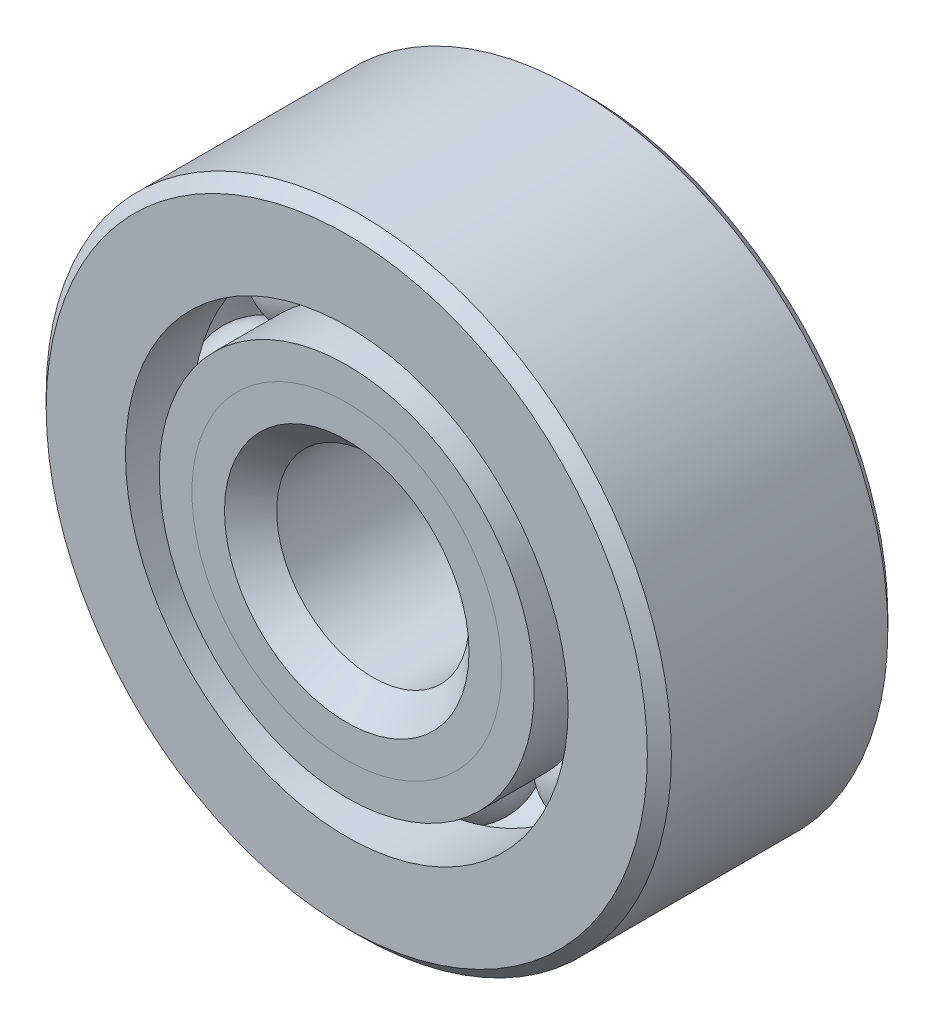
SolidWorks part; units mm, degrees
ref_plane "Front Plane" through (0, 0, 0) normal (0, 0, 1) x (1, 0, 0)
ref_plane "Top Plane" through (0, 0, 0) normal (0, 1, 0) x (1, 0, 0)
ref_plane "Right Plane" through (0, 0, 0) normal (1, 0, 0) x (0, 0, -1)
sketch "Sketch1" plane through (0, 0, 0) normal (1, 0, 0) x (0, 0, -1)
  line L0 (-2.5, 0) -> (2.5, 0) construction
  line L1 (0, 6.5) -> (0, -6.5) construction
  line L2 (2.25, 6.5) -> (-2.25, 6.5)
  line L3 (-2.25, 6.5) -> (-2.5, 6.25)
  line L4 (-2.5, 6.25) -> (-2.5, 4.6016)
  line L5 (-2.5, 4.6016) -> (-1.1111, 4.6016)
  line L6 (2.5, 4.6016) -> (1.1111, 4.6016)
  line L7 (2.5, 6.25) -> (2.5, 4.6016)
  line L8 (2.25, 6.5) -> (2.5, 6.25)
  line L9 (0, 6.5) -> (0, 4.25) construction
  line L10 (0, 4.25) -> (0, 2) construction
  line L11 (-2.5, -6.5) -> (2.5, -6.5) construction
  line L12 (0, -2) -> (0, 2) construction
  line L13 (2.5, -2) -> (2.5, 2) construction
  arc A0 (-1.1111, 4.6016) -> (1.1111, 4.6016) centre (0, 4.25) cw
  point P14 (0, 2)
  point P15 (0, -2)
  point P19 (0, -6.5)
  point P23 (0, 0)
  point P25 (2.5, 0)
  dimension "OD" = 13
  dimension "D1" = 45
  dimension "D2" = 0.25
  dimension "D3" = 2.2222
  dimension "D4" = 0.3516
  dimension "Width" = 5
  dimension "Shaft Dia" = 4
revolve "Revolve1" add sketch "Sketch1" angle 360 about L0
sketch "Sketch2" plane through (0, 0, 0) normal (1, 0, 0) x (0, 0, -1)
  line L0 (-2.5, 3.8984) -> (-1.1111, 3.8984)
  line L1 (-2.5, 6.25) -> (-2.5, -6.25) construction
  line L2 (-2.5, 3.8984) -> (-2.5, 3.2203)
  line L3 (-2.5, 3.2203) -> (-1.822, 2.5423)
  line L4 (-1.822, 2.5423) -> (0, 2.5423)
  line L5 (0, 6.5) -> (0, -6.5) construction
  line L6 (0, 2.5423) -> (0, 3.0846)
  line L7 (0, 3.0846) -> (0, 2) construction
  line L8 (-2.5, 3.8984) -> (-2.5, 2.5423) construction
  line L9 (-2.5, 2.5423) -> (-1.822, 2.5423) construction
  arc A0 (-1.1111, 3.8984) -> (0, 3.0846) centre (0, 4.25) ccw
  arc A1 (1.1111, 4.6016) -> (-1.1111, 4.6016) centre (0, 4.25) ccw construction
  circle A2 centre (0, 4.25) radius 1.1654 construction
  dimension "D1" = 45
revolve "Revolve2" add sketch "Sketch2" angle 360 about L0
sketch "Sketch3" plane through (0, 0, 0) normal (1, 0, 0) x (0, 0, -1)
  line L0 (-2.5, 3.2203) -> (-1.822, 2.5423)
  line L1 (-1.822, 2.5423) -> (0, 2.5423)
  line L2 (0, 2.5423) -> (0, 3.0846)
  line L3 (-2.5, 3.2203) -> (-2.5, 2.5423)
  line L4 (-2.5, 3.8984) -> (-2.5, 2.5423) construction
  line L5 (-2.5, 2.5423) -> (-1.9577, 2)
  line L6 (-1.9577, 2) -> (2.25, 2)
  line L7 (2.25, 6.5) -> (2.25, -6.5) construction
  line L8 (2.25, 2) -> (2.5, 2.25)
  line L9 (2.5, -6.25) -> (2.5, 6.25) construction
  line L10 (2.5, 2.25) -> (2.5, 3.8984)
  line L11 (2.5, 3.8984) -> (1.1111, 3.8984)
  line L13 (2.25, 6.5) -> (2.5, 6.25) construction
  circle A0 centre (0, 4.25) radius 1.1654 construction
  arc A1 (1.1111, 3.8984) -> (0, 3.0846) centre (0, 4.25) cw
revolve "Revolve3" add sketch "Sketch3" angle 360 about L0
sketch "Sketch4" plane through (0, 0, 0) normal (1, 0, 0) x (0, 0, -1)
  line L0 (-1.1654, 4.25) -> (1.1654, 4.25)
  circle A1 centre (0, 4.25) radius 1.1654 construction
  arc A2 (-1.1654, 4.25) -> (1.1654, 4.25) centre (0, 4.25) cw
  arc A3 (1.1111, 4.6016) -> (-1.1111, 4.6016) centre (0, 4.25) ccw construction
revolve "Revolve4" add sketch "Sketch4" angle 360 about L0
ref_axis "Axis1" through (0, 0, -2.5) along (0, 0, 1)
pattern_circular "CirPattern1" count 8 every 45 about axis through (0, 0, -2.5) along (0, 0, 1) of bodies 104
sketch "REF" plane through (0, 0, 0) normal (1, 0, 0) x (0, 0, -1)
  line L0 (2.25, 2) -> (2.5, 2.25) construction
  line L1 (-1.9577, 2) -> (2.25, 2) construction
  line L2 (-2.5, 2.5423) -> (-1.9577, 2) construction
  line L3 (2.25, 2) -> (2.5, 2.25) construction
  line L4 (-1.9577, 2) -> (2.25, 2) construction
  line L5 (-2.5, 2.5423) -> (-1.9577, 2) construction
  line L6 (-2.5, 0) -> (2.5, 0) construction
  line L7 (-2.5, 0) -> (2.5, 0) construction
  line L8 (2.25, -2) -> (2.5, -2.25) construction
  line L9 (-1.9577, -2) -> (2.25, -2) construction
  line L10 (-2.5, -2.5423) -> (-1.9577, -2) construction
ref_axis "Center Axis 1" through (0, 0, -2.25) along (0, 0, 1)
equation "\"D2@Sketch1\" = \"Width@Sketch1\"*.05"
equation "\"D3@Sketch1\" = \"Width@Sketch1\"/2.25"
equation "\"D4@Sketch1\" = (((\"OD@Sketch1\"-\"Width@Sketch1\")/2)/3.25)/3.5"
equation "\"D2@CirPattern1\" = 360/\"Balls@CirPattern1\""
